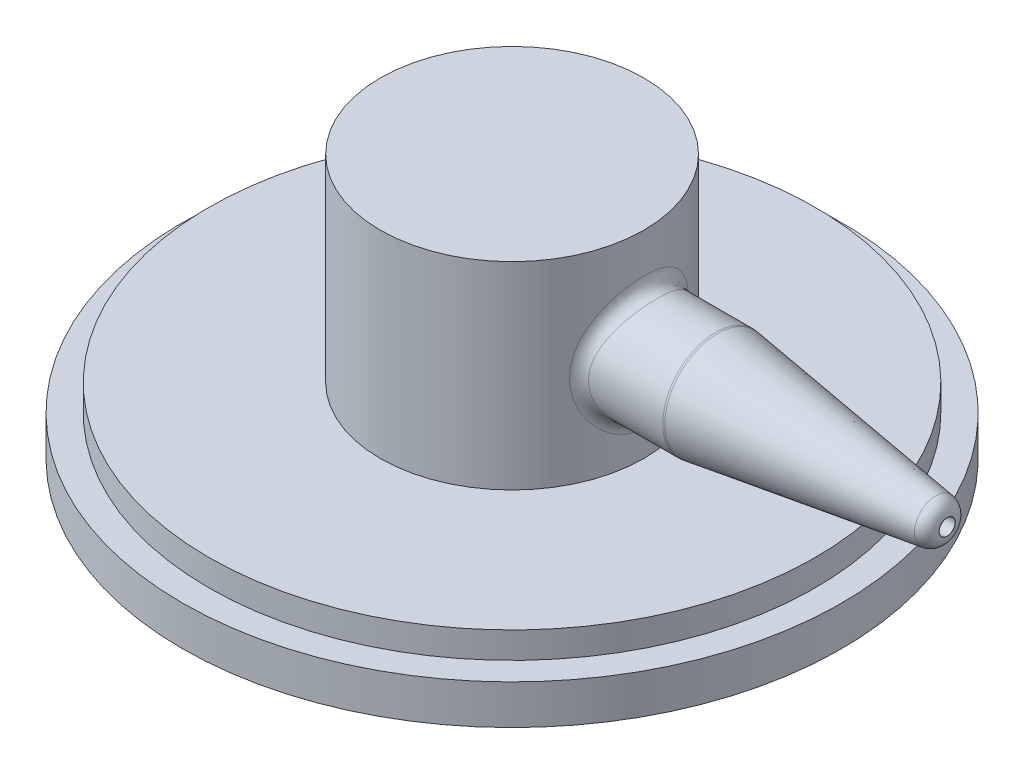
SolidWorks part; units mm, degrees
ref_plane "Ön Düzlem" through (0, 0, 0) normal (0, 0, 1) x (1, 0, 0)
ref_plane "Üst Düzlem" through (0, 0, 0) normal (0, 1, 0) x (1, 0, 0)
ref_plane "Sağ Düzlem" through (0, 0, 0) normal (1, 0, 0) x (0, 0, -1)
sketch "Sketch1" plane through (0, 0, 0) normal (0, 0, 1) x (1, 0, 0)
  line L0 (0, 20) -> (0, 0)
  line L8 (10, 20) -> (10, 5)
  line L11 (25, 0) -> (0, 0)
  line L13 (0, 20) -> (10, 20)
  line L14 (25, 0) -> (25, 3)
  line L15 (25, 3) -> (23, 3)
  line L16 (23, 3) -> (23, 5)
  line L19 (10, 5) -> (23, 5)
  dimension "D1" = 10
  dimension "D2" = 5
  dimension "D3" = 25
  dimension "D4" = 20
  dimension "D5" = 3
  dimension "D6" = 2
revolve "Revolve1" add sketch "Sketch1" angle 360 about L0
sketch "Sketch3" plane through (0, 0, 0) normal (1, 0, 0) x (0, 0, -1)
  line L0 (0, 0) -> (0, 64.7736) construction
  line L2 (-25, 0) -> (25, 0) construction
  circle A0 centre (0, 12) radius 4
  circle A1 centre (0, 12) radius 3
  dimension "D1" = 6
  dimension "D2" = 8
  dimension "D3" = 12
extrude "Boss-Extrude1" add sketch "Sketch3" along normal blind 25 contours A0
extrude "Boss-Extrude2" add sketch "Sketch3<5>" along normal blind 8 from surface contours A1 starting at face at (25, 12, -4)
sketch "Sketch3<5>" plane through (0, 0, 0) normal (1, 0, 0) x (0, 0, -1) same geometry as "Sketch3"
sketch "Sketch11" plane through (0, 0, 0) normal (0, 0, 1) x (1, 0, 0)
  line L0 (0, 4) -> (0, 0)
  line L1 (0, 0) -> (22.0729, 0)
  line L4 (0, 0) -> (0, 4.7847) construction
  arc A0 (0, 4) -> (22.0729, 0) centre (0.0014, -58.8935) cw
  dimension "D1" = 4
revolve "Cut-Revolve10" cut sketch "Sketch11" angle 360 about L4
sketch "Sketch15" plane through (0, 0, 0) normal (0, 1, 0) x (1, 0, 0)
  circle A0 centre (0, 0) radius 1.8
extrude "Cut-Extrude1" cut sketch "Sketch15" along normal blind 17 and the other way through all
sketch "Sketch16" plane through (0, 0, 0) normal (0, 0, 1) x (1, 0, 0)
  line L0 (33, 15) -> (33, 13.5)
  line L1 (33, 9) -> (33, 15) construction
  line L3 (25, 8) -> (25, 16) construction
  line L5 (33, 12) -> (25, 12) construction
  line L7 (25, 16) -> (10, 16) construction
  line L8 (15.5034, 16) -> (33, 13.5)
  line L9 (15.5034, 16) -> (33, 16)
  line L10 (33, 16) -> (33, 15)
revolve "Cut-Revolve12" cut sketch "Sketch16" angle 360 about L5
sketch "Sketch17" plane through (0, 0, 0) normal (0, 0, 1) x (1, 0, 0)
  line L1 (33, 12.6) -> (33, 12)
  line L4 (33, 12) -> (0, 12)
  line L10 (15.5034, 16) -> (15.5034, 14.8) construction
  line L11 (15.5034, 16) -> (15.5034, 8) construction
  line L13 (15.5034, 14.8) -> (0, 14.8)
  line L14 (0, 14.8) -> (0, 12)
  line L15 (15.5034, 14.8) -> (30.9004, 12.6)
  line L18 (33, 12.6) -> (30.9004, 12.6)
  dimension "D1" = 30.9004
  dimension "D2" = 12.6
  dimension "D3" = 14.8
  dimension "D4" = 33
  dimension "D5" = 12
revolve "Cut-Revolve13" cut sketch "Sketch17" angle 360 about L4
fillet "Fillet3" radius 1 3 edges at (33, 12, -1.5) (15.5034, 12, -4) (9.184, 12.5886, -3.9565)
